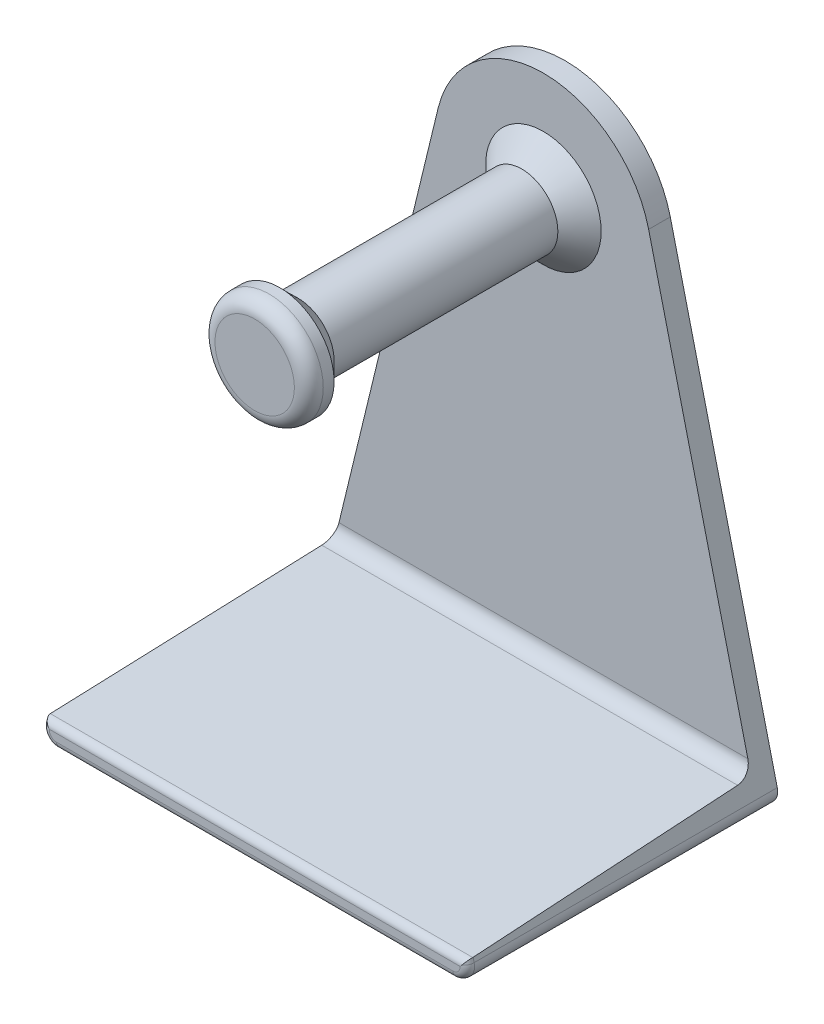
SolidWorks part; units mm, degrees
ref_plane "前视基准面" through (0, 0, 0) normal (0, 0, 1) x (1, 0, 0)
ref_plane "上视基准面" through (0, 0, 0) normal (0, 1, 0) x (1, 0, 0)
ref_plane "右视基准面" through (0, 0, 0) normal (1, 0, 0) x (0, 0, -1)
sketch "草图1" plane through (0, 0, 0) normal (0, 0, 1) x (1, 0, 0)
  line L0 (0, 15) -> (0, -60) construction
  line L1 (-14.5767, 3.5383) -> (-29.4, -57.5282)
  line L2 (-27.4564, -60) -> (27.4564, -60)
  line L3 (14.5767, 3.5383) -> (29.4, -57.5282)
  arc A0 (14.5767, 3.5383) -> (-14.5767, 3.5383) centre (0, 0) ccw
  arc A1 (-29.4, -57.5282) -> (-27.4564, -60) centre (-27.4564, -58) ccw
  arc A2 (29.4, -57.5282) -> (27.4564, -60) centre (27.4564, -58) cw
  point P10 (-30, -60)
  point P13 (30, -60)
  point P14 (0, 0)
  point P15 (0, 0)
  dimension "D1" = 30
  dimension "D2" = 2
  dimension "D3" = 60
  dimension "D4" = 60
extrude "凸台-拉伸1" add sketch "草图1" along normal blind 3
sketch "草图2" plane through (0, 0, 3) normal (0, 0, 1) x (1, 0, 0)
  circle A0 centre (0, 0) radius 5
  dimension "D1" = 10
extrude "凸台-拉伸2" add sketch "草图2" along normal blind 40
sketch "草图3" plane through (0, 0, 43) normal (0, 0, 1) x (1, 0, 0)
  circle A0 centre (0, 0) radius 7.5
  dimension "D1" = 15
extrude "凸台-拉伸3" add sketch "草图3" against normal blind 3
chamfer "倒角1" distance 3 angle 45 2 edges at (5, 0, 40) (5, 0, 3)
sketch "草图4" plane through (0, 0, 3) normal (0, 0, 1) x (1, 0, 0)
  line L0 (-29.2718, -57) -> (29.2718, -57)
  line L1 (-14.5767, 3.5383) -> (-29.4, -57.5282) construction
  line L2 (29.4, -57.5282) -> (14.5767, 3.5383) construction
  line L3 (-27.4564, -60) -> (27.4564, -60) construction
  line L7 (-27.4564, -60) -> (27.4564, -60)
  line L8 (29.4, -57.5282) -> (14.5767, 3.5383)
  line L9 (-14.5767, 3.5383) -> (-29.4, -57.5282)
  line L10 (-27.4564, -60) -> (27.4564, -60)
  line L11 (29.4, -57.5282) -> (29.2718, -57)
  line L12 (-29.2718, -57) -> (-29.4, -57.5282)
  arc A3 (-29.4, -57.5282) -> (-27.4564, -60) centre (-27.4564, -58) ccw
  arc A4 (27.4564, -60) -> (29.4, -57.5282) centre (27.4564, -58) ccw
  arc A5 (14.5767, 3.5383) -> (-14.5767, 3.5383) centre (0, 0) ccw
  arc A6 (-29.4, -57.5282) -> (-27.4564, -60) centre (-27.4564, -58) ccw
  arc A7 (27.4564, -60) -> (29.4, -57.5282) centre (27.4564, -58) ccw
  dimension "D1" = 3
  dimension "D2" = 0
extrude "凸台-拉伸4" add sketch "草图4" along normal up to surface (40 mm away) up to face at (7.5, 0, 43)
sketch "草图6" plane through (0, 0, 0) normal (1, 0, 0) x (0, 0, -1)
  line L0 (-43, -57) -> (-3, -55)
  line L1 (-3, -57) -> (-3, 3.5383) construction
  line L2 (-23, -57) -> (-23, -56) construction
  line L3 (-43, -57) -> (-3, -57) construction
  line L4 (-3, -57) -> (-3, -55)
  line L5 (-43, -57) -> (-3, -57)
  dimension "D1" = 1
  dimension "D2" = 20
extrude "凸台-拉伸5" add sketch "草图6" along normal up to vertex (30 mm away) and the other way up to vertex (30 mm away) up to point (30, -60, 0) other way up to point (-30, -60, 0)
extrude "切除-拉伸1" cut sketch "草图1<2>" along normal through all flip side to cut contours L3 A2 L2 A1 L1 A0
sketch "草图1<2>" plane through (0, 0, 0) normal (0, 0, 1) x (1, 0, 0) same geometry as "草图1"
fillet "圆角1" radius 2 1 edges at (0, -55, 3)
fillet "圆角2" radius 1 4 edges at (29.0286, -59.2362, 43) (0, -60, 43) (-29.0286, -59.2362, 43) (0, -57, 43)
fillet "圆角3" radius 2 1 edges at (7.5, 0, 43)
